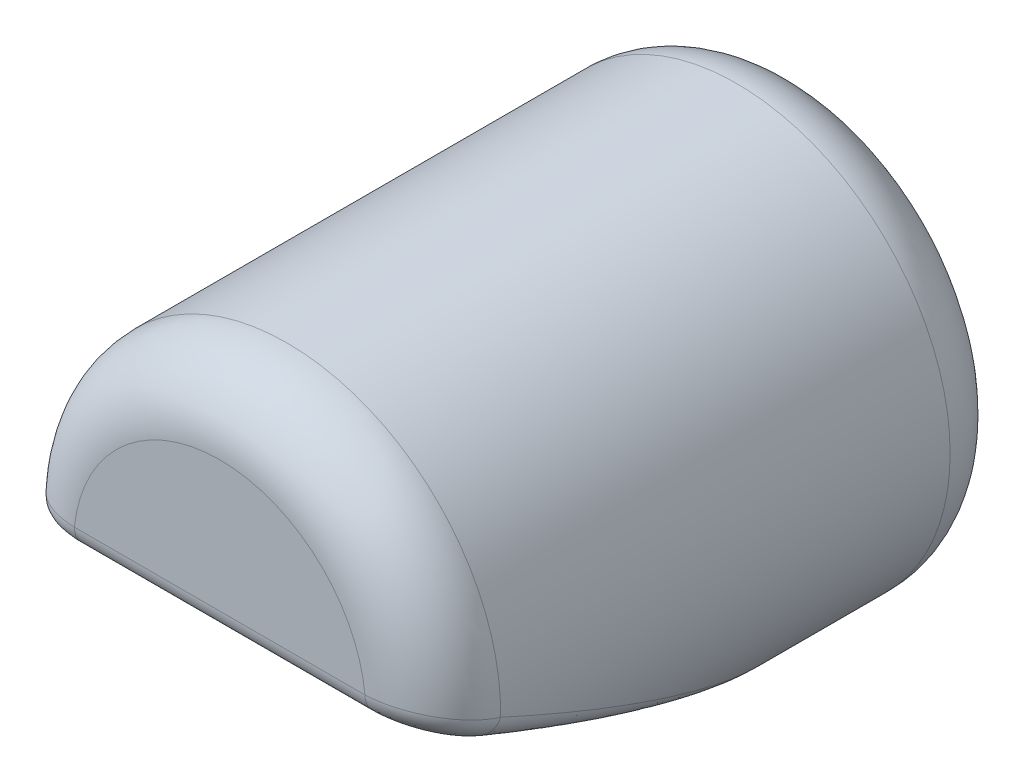
SolidWorks part; units mm, degrees
ref_plane "Front Plane" through (0, 0, 0) normal (0, 0, 1) x (1, 0, 0)
ref_plane "Top Plane" through (0, 0, 0) normal (0, 1, 0) x (1, 0, 0)
ref_plane "Right Plane" through (0, 0, 0) normal (1, 0, 0) x (0, 0, -1)
sketch "Sketch2" plane through (0, 0, 0) normal (0, 0, 1) x (1, 0, 0)
  circle A0 centre (0, 0) radius 9.5
  dimension "D1" = 19
extrude "Boss-Extrude1" add sketch "Sketch2" along normal blind 26
ref_point "Point1"
ref_point "Point2"
fillet "Fillet1" radius 3 2 edges at (9.5, 0, 26) (9.5, 0, 0)
sketch "Sketch3" plane through (0, 0, 0) normal (1, 0, 0) x (0, 0, -1)
  line L0 (-26, 0) -> (-3, -9.5)
  line L1 (-3, -9.5) -> (-3, -10.4048)
  line L2 (-3, -10.4048) -> (-26, -10.4048)
  line L3 (-26, 0) -> (-26, 1000) construction
  line L4 (-26, 50) -> (-26, -50) construction
  line L5 (-26, -10.4048) -> (-26, 0)
extrude "Cut-Extrude1" cut sketch "Sketch3" against normal blind 10 and the other way blind 10
fillet "Fillet2" radius 1 5 edges at (6.2641, -7.1422, 8.7084) (8.1481, -0.2044, 25.5051) (-6.2641, -7.1422, 8.7084) (-8.814, -0.4565, 24.8948) (0, 0, 26)
